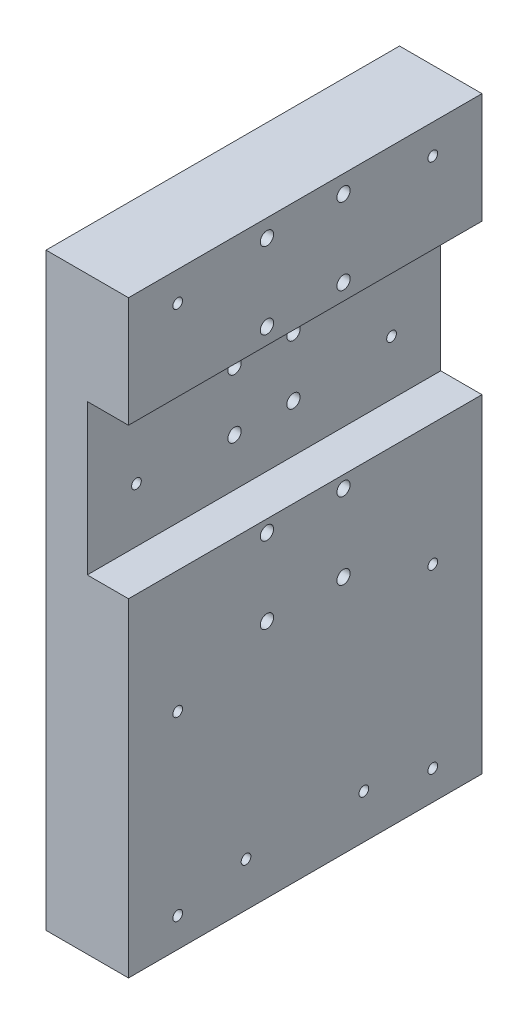
SolidWorks part; units mm, degrees
ref_plane "Front Plane" through (0, 0, 0) normal (0, 0, 1) x (1, 0, 0)
ref_plane "Top Plane" through (0, 0, 0) normal (0, 1, 0) x (1, 0, 0)
ref_plane "Right Plane" through (0, 0, 0) normal (1, 0, 0) x (0, 0, -1)
sketch "Sketch1" plane through (0, 0, 0) normal (0, 0, 1) x (1, 0, 0)
  line L0 (0, 0) -> (0, 200)
  line L1 (0, 200) -> (28, 200)
  line L2 (28, 200) -> (28, 162.5)
  line L3 (14, 162.5) -> (14, 111.5)
  line L4 (14, 162.5) -> (28, 162.5)
  line L5 (14, 111.5) -> (28, 111.5)
  line L6 (28, 111.5) -> (28, 0)
  line L7 (28, 0) -> (0, 0)
  line L8 (-49.525, 137) -> (95.9642, 137) construction
  point P12 (14, 137)
  dimension "D1" = 200
  dimension "D2" = 25.5
  dimension "D4" = 28
  dimension "D6" = 63
extrude "Boss-Extrude1" add sketch "Sketch1" along normal blind 120 contours L0 L1 L2 L4 L3 L5 L6 L7
sketch "Sketch2" plane through (0, 0, 0) normal (-1, 0, 0) x (0, 0, 1)
  line L0 (60, 200) -> (60, 0) construction
  line L1 (120, 200) -> (0, 200) construction
  line L2 (120, 0) -> (0, 0) construction
  point P6 (73, 194)
  point P7 (73, 168)
  point P8 (70, 147.7)
  point P9 (70, 127.7)
  point P10 (73, 107.4)
  point P11 (73, 81.4)
  point P12 (47, 81.4)
  point P13 (47, 107.4)
  point P14 (50, 127.7)
  point P15 (50, 147.7)
  point P16 (47, 168)
  point P17 (47, 194)
  dimension "D1" = 6
  dimension "D2" = 26
  dimension "D3" = 46.3
  dimension "D4" = 20
  dimension "D5" = 20.3
  dimension "D6" = 26
  dimension "D7" = 13
  dimension "D8" = 10
hole_wizard "CBORE for M4 SHCS4" positions "3DSketch2" profile "Sketch4" counterbore size "M4" standard "ANSI Metric" end condition through all
sketch3d "3DSketch2"
  point P0 (0, 194, 73)
  point P3 (0, 168, 73)
  point P6 (0, 147.7, 70)
  point P9 (0, 127.7, 70)
  point P12 (0, 107.4, 73)
  point P15 (0, 81.4, 73)
  point P18 (0, 81.4, 47)
  point P21 (0, 107.4, 47)
  point P24 (0, 127.7, 50)
  point P27 (0, 147.7, 50)
  point P30 (0, 168, 47)
  point P33 (0, 194, 47)
sketch "Sketch4" plane through (0, 194, 73) normal (0, 1, 0) x (0, 0, 1)
  line L0 (0, 0) -> (0, 28)
  line L1 (0, 28) -> (2.25, 28)
  line L3 (2.25, 28) -> (2.25, 4)
  line L4 (2.25, 4) -> (4, 4)
  line L5 (4, 4) -> (4, 0)
  line L7 (4, 0) -> (0, 0)
  line L11 (0, -6.35) -> (0, 107.95) construction
  dimension "Thru Hole Dia." = 4.5
  dimension "Thru Hole Depth" = 28
  dimension "C'Bore Dia." = 8
  dimension "C'Bore Depth" = 4
sketch "Sketch5" plane through (0, 0, 0) normal (-1, 0, 0) x (0, 0, 1)
  line L0 (16.7, 200) -> (16.7, 0) construction
  line L1 (120, 200) -> (0, 200) construction
  line L2 (120, 0) -> (0, 0) construction
  line L3 (60, 200) -> (60, 0) construction
  line L4 (60, 200) -> (60, 0) construction
  line L5 (103.3, 200) -> (103.3, 0) construction
  point P12 (16.7, 190)
  point P13 (103.3, 10)
  point P14 (16.7, 130)
  point P15 (16.7, 70)
  point P16 (16.7, 10)
  point P17 (103.3, 70)
  point P18 (103.3, 130)
  point P19 (103.3, 190)
  dimension "D1" = 43.3
  dimension "D2" = 10
  dimension "D3" = 4
hole_wizard "M4 Tapped Hole1" positions "3DSketch3" profile "Sketch6" tap size "M4" standard "ISO" end condition through all
sketch3d "3DSketch3"
  point P0 (0, 190, 16.7)
  point P3 (0, 130, 16.7)
  point P6 (0, 70, 16.7)
  point P9 (0, 10, 16.7)
  point P12 (0, 10, 103.3)
  point P15 (0, 70, 103.3)
  point P18 (0, 130, 103.3)
  point P21 (0, 190, 103.3)
sketch "Sketch6" plane through (0, 190, 16.7) normal (0, 1, 0) x (0, 0, 1)
  line L0 (0, 0) -> (0, 28)
  line L1 (0, 28) -> (1.65, 28)
  line L2 (1.65, 28) -> (1.65, 0)
  line L5 (1.65, 0) -> (0, 0)
  line L11 (0, -6.35) -> (0, 107.95) construction
  dimension "Thread Major Dia." = 3.3
  dimension "Thru Tap Drill Depth" = 28
ref_plane "Plane1" through (0, 0, 60) normal (0, 0, -1) x (-1, 0, 0)
sketch "Sketch7" plane through (0, 0, 0) normal (0, -1, 0) x (1, 0, 0)
  line L0 (14, 120) -> (14, 0) construction
  line L1 (28, 120) -> (0, 120) construction
  line L2 (28, 0) -> (0, 0) construction
  line L3 (28, 60) -> (0, 60) construction
  line L4 (28, 120) -> (28, 0) construction
  line L5 (0, 120) -> (0, 0) construction
  point P12 (14, 60)
  point P13 (14, 90)
  point P14 (14, 30)
  dimension "D1" = 30
hole_wizard "M5 Tapped Hole1" positions "3DSketch4" profile "Sketch8" tap size "M5" standard "ISO"
sketch3d "3DSketch4"
  point P0 (14, 0, 90)
  point P3 (14, 0, 60)
  point P6 (14, 0, 30)
sketch "Sketch8" plane through (14, 0, 90) normal (1, 0, 0) x (0, 0, -1)
  line L0 (0, 0) -> (0, 18.6618)
  line L1 (0, 18.6618) -> (2.1, 17.4)
  line L2 (2.1, 17.4) -> (2.1, 0)
  line L5 (2.1, 0) -> (0, 0)
  line L10 (0, 18.6618) -> (-2.1, 17.4) construction
  line L11 (0, -6.35) -> (0, 107.95) construction
  dimension "Tap Drill Dia." = 4.2
  dimension "Tap Drill Depth" = 17.4
  dimension "Drill Angle" = 118
sketch "Sketch9" plane through (28, 0, 0) normal (1, 0, 0) x (0, 0, -1)
  line L0 (-40.1, 23.78) -> (-40.1, -18.6105) construction
  line L1 (-80.1, 23.78) -> (-80.1, -18.6105) construction
  line L8 (0, -10) -> (-120, -10) construction
  line L9 (0, -20) -> (0, 0) construction
  line L10 (-120, -20) -> (-120, 0) construction
  line L11 (-120, 0) -> (0, 0) construction
  point P6 (-40.1, -10)
  point P7 (-80.1, -10)
  point P8 (-40.1, 15)
  point P9 (-80.1, 15)
  dimension "D1" = 15
hole_wizard "M4 Tapped Hole2" positions "3DSketch5" profile "Sketch10" tap size "M4" standard "ISO" end condition through all
sketch3d "3DSketch5"
  point P0 (28, 15, 80.1)
  point P3 (28, 15, 40.1)
sketch "Sketch10" plane through (28, 15, 80.1) normal (0, 1, 0) x (0, 0, -1)
  line L0 (0, 0) -> (0, 28)
  line L1 (0, 28) -> (1.65, 28)
  line L2 (1.65, 28) -> (1.65, 0)
  line L5 (1.65, 0) -> (0, 0)
  line L11 (0, -6.35) -> (0, 107.95) construction
  dimension "Thread Major Dia." = 3.3
  dimension "Thru Tap Drill Depth" = 28
